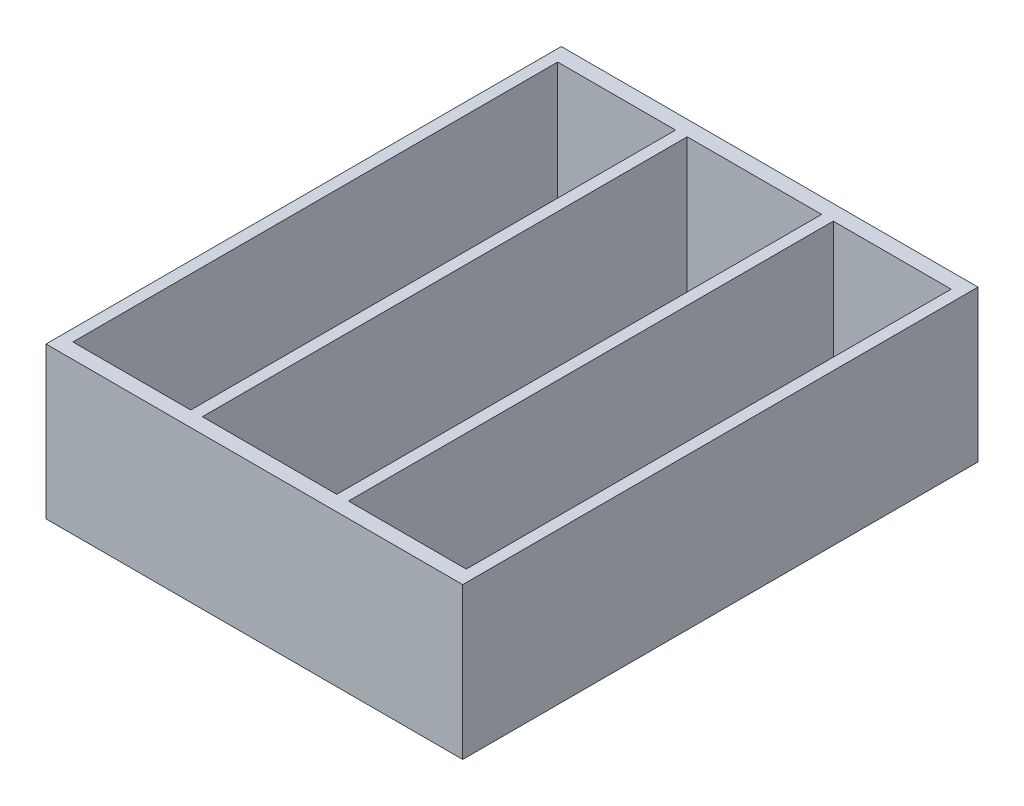
SolidWorks part; units mm, degrees
ref_plane "前视基准面" through (0, 0, 0) normal (0, 0, 1) x (1, 0, 0)
ref_plane "上视基准面" through (0, 0, 0) normal (0, 1, 0) x (1, 0, 0)
ref_plane "右视基准面" through (0, 0, 0) normal (1, 0, 0) x (0, 0, -1)
other "Configuration Table"
sketch "草图1" plane through (0, 0, 0) normal (0, 1, 0) x (1, 0, 0)
  line L5 (-23.25, -28.75) -> (23.25, -28.75)
  line L6 (-23.25, -28.75) -> (-23.25, 28.75)
  line L59 (-23.25, 28.75) -> (23.25, 28.75)
  line L60 (23.25, -28.75) -> (23.25, 28.75)
  line L61 (-23.25, -28.75) -> (23.25, 28.75) construction
  line L62 (-23.25, 28.75) -> (23.25, -28.75) construction
  point P0 (0, 0)
  dimension "D1" = 46.5
  dimension "D2" = 57.5
extrude "凸台-拉伸1" add sketch "草图1" along normal blind 1.6 contours L60 L59 L6 L5
sketch "草图2" plane through (0, 1.6, 0) normal (0, 1, 0) x (1, 0, 0)
  line L0 (-23.25, 28.75) -> (23.25, 28.75) construction
  line L1 (-8.8, 28.75) -> (-7.5, 28.75)
  line L2 (-8.8, 28.75) -> (-8.8, -28.75)
  line L3 (-8.8, -28.75) -> (-7.5, -28.75)
  line L4 (-7.5, 28.75) -> (-7.5, -28.75)
  line L5 (-23.25, -28.75) -> (23.25, -28.75) construction
  line L6 (0, 0) -> (-7.5, 0) construction
  line L7 (8.8, 28.75) -> (7.5, 28.75)
  line L8 (8.8, 28.75) -> (8.8, -28.75)
  line L9 (8.8, -28.75) -> (7.5, -28.75)
  line L10 (7.5, 28.75) -> (7.5, -28.75)
  line L11 (0, 0) -> (7.5, 0) construction
  line L13 (-23.25, 28.75) -> (-21.95, 28.75)
  line L14 (-23.25, 28.75) -> (-23.25, -28.75)
  line L15 (-23.25, -28.75) -> (-21.95, -28.75)
  line L16 (-21.95, 28.75) -> (-21.95, -28.75)
  line L17 (23.25, -28.75) -> (21.95, -28.75)
  line L18 (23.25, -28.75) -> (23.25, 28.75)
  line L19 (23.25, 28.75) -> (21.95, 28.75)
  line L20 (21.95, -28.75) -> (21.95, 28.75)
  line L21 (-21.95, 28.75) -> (-8.8, 28.75)
  line L22 (-21.95, 28.75) -> (-21.95, 27.05)
  line L23 (-21.95, 27.05) -> (-8.8, 27.05)
  line L24 (-8.8, 28.75) -> (-8.8, 27.05)
  line L25 (-7.5, 28.75) -> (7.5, 28.75)
  line L26 (-7.5, 28.75) -> (-7.5, 27.05)
  line L27 (-7.5, 27.05) -> (7.5, 27.05)
  line L28 (7.5, 28.75) -> (7.5, 27.05)
  line L29 (8.8, 28.75) -> (21.95, 28.75)
  line L30 (8.8, 28.75) -> (8.8, 27.05)
  line L31 (8.8, 27.05) -> (21.95, 27.05)
  line L32 (21.95, 28.75) -> (21.95, 27.05)
  line L33 (-21.95, -28.75) -> (-8.8, -28.75)
  line L34 (-21.95, -28.75) -> (-21.95, -27.05)
  line L35 (-21.95, -27.05) -> (-8.8, -27.05)
  line L36 (-8.8, -28.75) -> (-8.8, -27.05)
  line L37 (-7.5, -28.75) -> (7.5, -28.75)
  line L38 (-7.5, -28.75) -> (-7.5, -27.05)
  line L39 (-7.5, -27.05) -> (7.5, -27.05)
  line L40 (7.5, -28.75) -> (7.5, -27.05)
  line L41 (8.8, -28.75) -> (21.95, -28.75)
  line L42 (8.8, -28.75) -> (8.8, -27.05)
  line L43 (8.8, -27.05) -> (21.95, -27.05)
  line L44 (21.95, -28.75) -> (21.95, -27.05)
  line M11 (-23.25, -28.75) -> (23.25, -28.75)
  line M12 (23.25, -28.75) -> (23.25, 28.75)
  line M13 (23.25, 28.75) -> (-23.25, 28.75)
  line M14 (-23.25, 28.75) -> (-23.25, -28.75)
  dimension "D1" = 16.3
  dimension "D2" = 1.3
  dimension "D3" = 1.7
extrude "凸台-拉伸2" add sketch "草图2" along normal blind 15.3 contours L4 L2 M13 M11 | L16 L23 L2 M13 | L16 M13 M14 M11 | L4 L27 L10 M13 | L10 L8 M13 M11 | L8 L31 L20 M13 | L20 M11 M12 M13 | L43 L8 L20 M11 | L39 L4 L10 M11 | L35 L16 L2 M11 region at (-8.15, 1.6, 0) region at (-15.375, 1.6, -27.9) region at (0, 1.6, -27.9) region at (-22.6, 1.6, 0) region at (8.15, 1.6, 0) region at (-15.375, 1.6, 27.9) region at (0, 1.6, 27.9) region at (15.375, 1.6, -27.9) region at (22.6, 1.6, 0) region at (15.375, 1.6, 27.9)
sketch "草图3" plane through (0, 0, 0) normal (0, -1, 0) x (1, 0, 0)
  line L0 (-13.6, 0) -> (13.6, 0) construction
  circle A0 centre (-15.1, 0) radius 1.5
  circle A1 centre (15.1, 0) radius 1.5
  circle A2 centre (-15.1, 0) radius 2.5
  circle A3 centre (15.1, 0) radius 2.5
  dimension "D1" = 3
  dimension "D3" = 5
  dimension "D2" = 27.2
extrude "切除-拉伸1" cut sketch "草图3" against normal through all contours A1 | A0
extrude "切除-拉伸2" cut sketch "草图3<3>" along normal blind 0.8 from surface contours A2 | A3 starting at face at (-15.1, 1.6, 1.5)
sketch "草图3<3>" plane through (0, 0, 0) normal (0, -1, 0) x (1, 0, 0) same geometry as "草图3"
